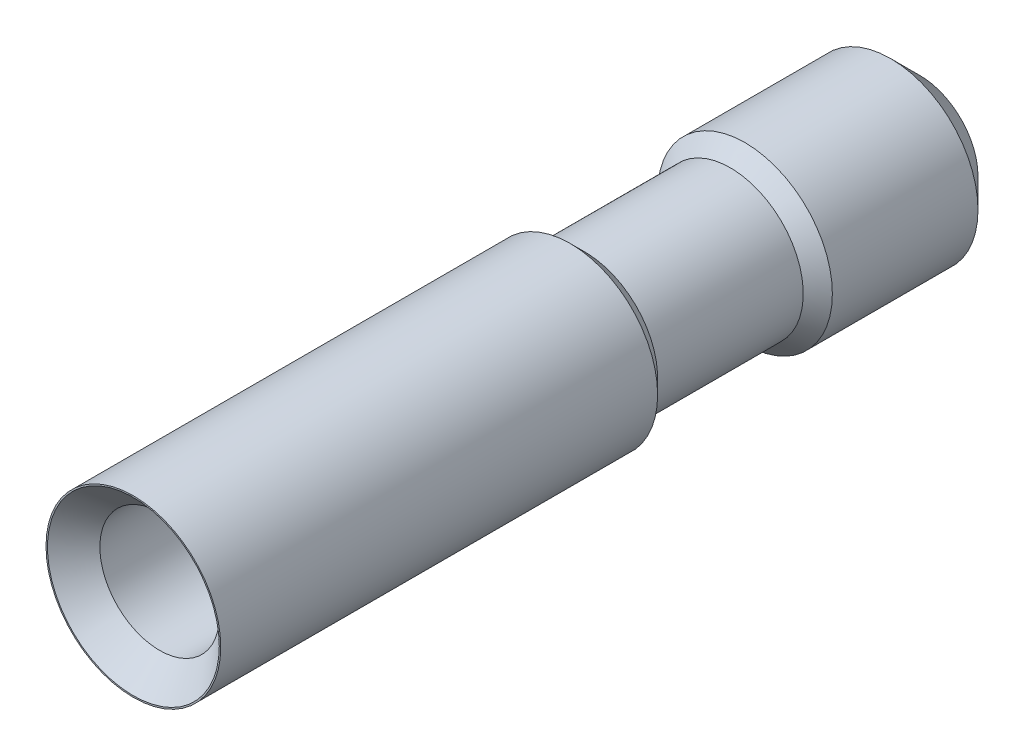
SolidWorks part; units mm, degrees
material "1.4000 (X6Cr13)"
ref_plane "Plan de face" through (0, 0, 0) normal (0, 0, 1) x (1, 0, 0)
ref_plane "Plan de dessus" through (0, 0, 0) normal (0, 1, 0) x (1, 0, 0)
ref_plane "Plan de droite" through (0, 0, 0) normal (1, 0, 0) x (0, 0, -1)
sketch "Esquisse1" plane through (0, 0, 0) normal (0, 0, 1) x (1, 0, 0)
  circle A0 centre (0, 0) radius 3
  dimension "D1" = 6
extrude "Boss.-Extru.1" add sketch "Esquisse1" along normal blind 27 contours A0
cosmetic thread "Représentation de filetage1" parameters "D1"=6, "D2"=4.891
sketch "Esquisse7" plane through (0, 0, 27) normal (0, 0, 1) x (1, 0, 0)
  circle A1 centre (0, 0) radius 2.05
  dimension "D1" = 4.1
hole_wizard "Diamètre du perçage Ø2.0 (2)1" positions "Esquisse5" profile "Esquisse4" hole size "Ø2.0" standard "ISO"
sketch "Esquisse5" plane through (0, 0, 0) normal (0, 0, -1) x (-1, 0, 0)
  point P0 (0, 0)
sketch "Esquisse4" plane through (0, 0, 0) normal (1, 0, 0) x (0, 1, 0)
  line L0 (0, 0) -> (0, 3)
  line L1 (0, 3) -> (1, 3)
  line L2 (1, 3) -> (1, 0)
  line L5 (1, 0) -> (0, 0)
  line L10 (0, 3) -> (-1, 3) construction
  line L11 (0, -6.35) -> (0, 107.95) construction
  dimension "Diamètre du perçage" = 2
  dimension "Profondeur du perçage" = 3
  dimension "Angle de pointe" = 180
sketch "Esquisse6" plane through (0, 0, 27) normal (0, 0, 1) x (1, 0, 0)
  line L1 (-6.0949, -5.2635) -> (5.6553, -5.2635)
  line L2 (-6.0949, -5.2635) -> (-6.0949, 6.1211)
  line L3 (-6.0949, 6.1211) -> (5.6553, 6.1211)
  line L4 (5.6553, -5.2635) -> (5.6553, 6.1211)
  circle A0 centre (0, 0) radius 2.5
  dimension "D1" = 5
extrude "Enlèv. mat.-Extru.1" cut sketch "Esquisse6" against normal blind 6 from offset 15 offset against normal yes
chamfer "Chanfrein1" distance 1 angle 45 1 edges at (3, 0, 0)
chamfer "Chanfrein2" distance 0.5 angle 45 2 edges at (2.5, 0, 6) (2.5, 0, 12)
hole_wizard "Diamètre du perçage Ø4.1 (4.1)1" positions "Esquisse9" profile "Esquisse8" hole size "Ø4.1" standard "ISO"
sketch "Esquisse9" plane through (0, 0, 27) normal (0, 0, 1) x (1, 0, 0)
  point P0 (0, 0)
sketch "Esquisse8" plane through (0, 0, 27) normal (1, 0, 0) x (0, -1, 0)
  line L0 (0, 0) -> (0, 24)
  line L1 (0, 24) -> (2.05, 24)
  line L2 (2.05, 24) -> (2.05, 0)
  line L5 (2.05, 0) -> (0, 0)
  line L10 (0, 24) -> (-2.05, 24) construction
  line L11 (0, -6.35) -> (0, 107.95) construction
  dimension "Diamètre du perçage" = 4.1
  dimension "Profondeur du perçage" = 24
  dimension "Angle de pointe" = 180
chamfer "Chanfrein3" distance 0.9 angle 45 1 edges at (2.05, 0, 27)
